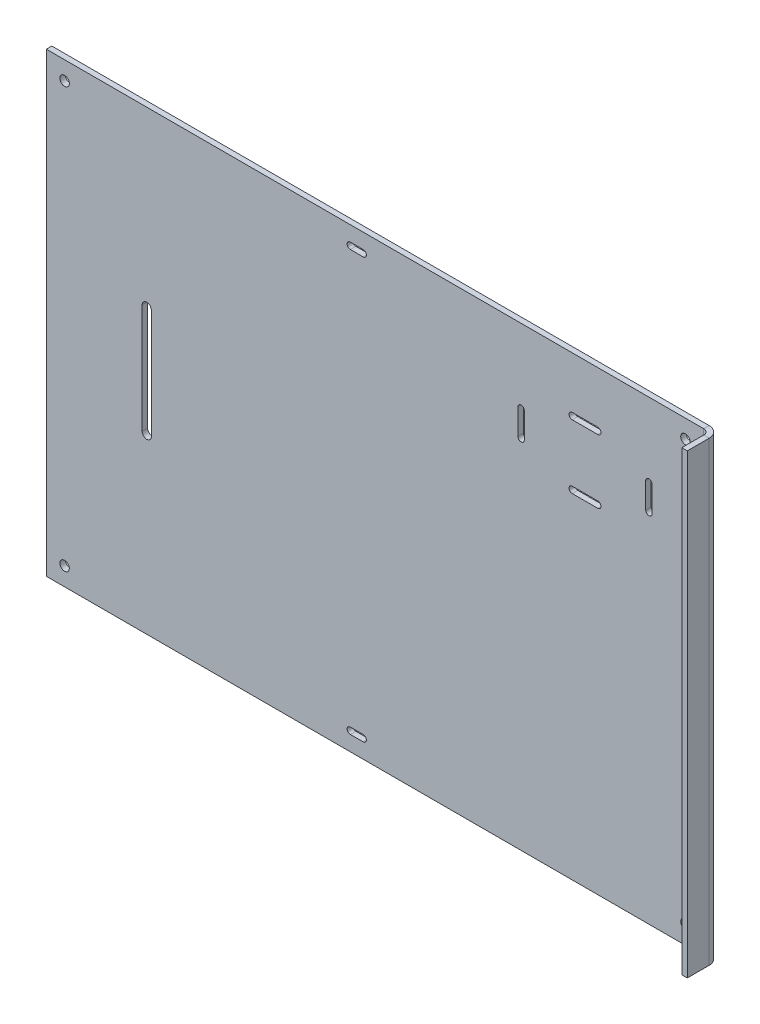
SolidWorks part; units mm, degrees
note: The reader was unsure of these and kept them because the rebuilt part matched: flange length of "Edge-Flange1".
ref_plane "Front Plane" through (0, 0, 0) normal (0, 0, 1) x (1, 0, 0)
ref_plane "Top Plane" through (0, 0, 0) normal (0, 1, 0) x (1, 0, 0)
ref_plane "Right Plane" through (0, 0, 0) normal (1, 0, 0) x (0, 0, -1)
sketch "Sketch1" plane through (0, 0, 0) normal (0, 0, 1) x (1, 0, 0)
  line L0 (180, 125) -> (-180, -125) construction
  line L1 (-180, 125) -> (180, 125)
  line L2 (-180, 125) -> (-180, -125)
  line L3 (-180, -125) -> (180, -125)
  line L4 (180, 125) -> (180, -125)
  point P4 (0, 0)
  dimension "D1" = 360
  dimension "D2" = 250
base flange "Base-Flange1" sketch "Sketch1" thickness 3 reverse thickness direction no parameters "D1"=3
hole_wizard "#6 (0.204) Diameter Slot1" positions "Sketch7" profile "Sketch6" size "#6" standard "ANSI Inch" slot yes end condition through all
sketch "Sketch7" plane through (0, 0, 0) normal (0, 0, 1) x (1, 0, 0)
  line L0 (-180, 125) -> (-180, -125) construction
  line L1 (180, 125) -> (-180, 125) construction
  line L2 (180, -125) -> (180, 125) construction
  line L3 (-180, -125) -> (180, -125) construction
  point P0 (-170, -115)
  point P2 (-170, 115)
  point P4 (170, 115)
  point P6 (170, -115)
  dimension "D1" = 10
  dimension "D2" = 10
  dimension "D3" = 10
  dimension "D4" = 10
  dimension "D5" = 10
  dimension "D6" = 10
  dimension "D7" = 10
  dimension "D8" = 10
sketch "Sketch6" plane through (-170, -115, 0) normal (1, 0, 0) x (0, -1, 0)
  line L0 (0, 0) -> (0, 3)
  line L1 (0, 3) -> (2.5908, 3)
  line L2 (2.5908, 3) -> (2.5908, 0)
  line L5 (2.5908, 0) -> (0, 0)
  line L11 (0, -6.35) -> (0, 107.95) construction
  dimension "Thru Hole Dia." = 5.1816
  dimension "Thru Hole Depth" = 3
sketch "Sketch8" plane through (0, 0, 0) normal (0, 0, 1) x (1, 0, 0)
  line L0 (-13.5, -115) -> (-6.5, -115) construction
  line L1 (-13.5, -113.25) -> (-6.5, -113.25)
  line L2 (-13.5, -116.75) -> (-6.5, -116.75)
  line L3 (-180, -125) -> (180, -125) construction
  line L4 (-180, 125) -> (-180, -125) construction
  arc A0 (-13.5, -113.25) -> (-13.5, -116.75) centre (-13.5, -115) ccw
  arc A1 (-6.5, -116.75) -> (-6.5, -113.25) centre (-6.5, -115) ccw
  point P2 (-10, -115)
  dimension "D1" = 10
  dimension "D2" = 170
extrude "Cut-Extrude1" cut sketch "Sketch8" against normal blind 10
sketch "Sketch9" plane through (0, 0, 0) normal (0, 0, 1) x (1, 0, 0)
  line L0 (-13.5, 115) -> (-6.5, 115) construction
  line L1 (-13.5, 116.75) -> (-6.5, 116.75)
  line L2 (-13.5, 113.25) -> (-6.5, 113.25)
  line L3 (180, 125) -> (-180, 125) construction
  line L4 (-180, 125) -> (-180, -125) construction
  arc A0 (-13.5, 116.75) -> (-13.5, 113.25) centre (-13.5, 115) ccw
  arc A1 (-6.5, 113.25) -> (-6.5, 116.75) centre (-6.5, 115) ccw
  point P2 (-10, 115)
  dimension "D1" = 10
  dimension "D2" = 170
extrude "Cut-Extrude2" cut sketch "Sketch9" against normal blind 10
sketch "Sketch10" plane through (0, 0, 0) normal (0, 0, 1) x (1, 0, 0)
  line L0 (150, 84.5) -> (150, 70.5) construction
  line L1 (151.75, 84.5) -> (151.75, 70.5)
  line L2 (148.25, 84.5) -> (148.25, 70.5)
  line L3 (180, -125) -> (180, 125) construction
  line L4 (180, 125) -> (-180, 125) construction
  arc A0 (151.75, 84.5) -> (148.25, 84.5) centre (150, 84.5) ccw
  arc A1 (148.25, 70.5) -> (151.75, 70.5) centre (150, 70.5) ccw
  point P2 (150, 77.5)
  dimension "D1" = 30
  dimension "D2" = 47.5
extrude "Cut-Extrude4" cut sketch "Sketch10" against normal blind 10
sketch "Sketch11" plane through (0, 0, 0) normal (0, 0, 1) x (1, 0, 0)
  line L0 (108, 95) -> (122, 95) construction
  line L1 (108, 96.75) -> (122, 96.75)
  line L2 (108, 93.25) -> (122, 93.25)
  line L3 (180, 125) -> (-180, 125) construction
  line L4 (180, -125) -> (180, 125) construction
  arc A0 (108, 96.75) -> (108, 93.25) centre (108, 95) ccw
  arc A1 (122, 93.25) -> (122, 96.75) centre (122, 95) ccw
  point P2 (115, 95)
  dimension "D1" = 30
  dimension "D2" = 65
extrude "Cut-Extrude5" cut sketch "Sketch11" against normal blind 10
sketch "Sketch12" plane through (0, 0, 0) normal (0, 0, 1) x (1, 0, 0)
  line L0 (108, 60) -> (122, 60) construction
  line L1 (108, 61.75) -> (122, 61.75)
  line L2 (108, 58.25) -> (122, 58.25)
  line L3 (180, -125) -> (180, 125) construction
  line L4 (180, 125) -> (-180, 125) construction
  arc A0 (108, 61.75) -> (108, 58.25) centre (108, 60) ccw
  arc A1 (122, 58.25) -> (122, 61.75) centre (122, 60) ccw
  point P2 (115, 60)
  dimension "D1" = 65
  dimension "D2" = 65
extrude "Cut-Extrude6" cut sketch "Sketch12" against normal blind 10
sketch "Sketch13" plane through (0, 0, 0) normal (0, 0, 1) x (1, 0, 0)
  line L0 (80, 84.5) -> (80, 70.5) construction
  line L1 (81.75, 84.5) -> (81.75, 70.5)
  line L2 (78.25, 84.5) -> (78.25, 70.5)
  line L3 (180, -125) -> (180, 125) construction
  line L4 (180, 125) -> (-180, 125) construction
  arc A0 (81.75, 84.5) -> (78.25, 84.5) centre (80, 84.5) ccw
  arc A1 (78.25, 70.5) -> (81.75, 70.5) centre (80, 70.5) ccw
  point P2 (80, 77.5)
  dimension "D1" = 100
  dimension "D2" = 47.5
extrude "Cut-Extrude7" cut sketch "Sketch13" against normal blind 10
sketch "Sketch14" plane through (0, 0, 0) normal (0, 0, 1) x (1, 0, 0)
  line L0 (-125, 30) -> (-125, -30) construction
  line L1 (-122.5, 30) -> (-122.5, -30)
  line L2 (-127.5, 30) -> (-127.5, -30)
  line L3 (-180, 125) -> (-180, -125) construction
  line L4 (180, 125) -> (-180, 125) construction
  arc A0 (-122.5, 30) -> (-127.5, 30) centre (-125, 30) ccw
  arc A1 (-127.5, -30) -> (-122.5, -30) centre (-125, -30) ccw
  point P2 (-125, 0)
  dimension "D1" = 55
  dimension "D2" = 125
extrude "Cut-Extrude8" cut sketch "Sketch14" against normal blind 10
edge flange "Edge-Flange1" sketch "Sketch18" flange angle 90 flange length 18 flange position bend outside bend radius 3 thickness 3 parameters "D6"=10
sketch "Sketch18" plane through (180, 0, 0) normal (1, 0, 0) x (0, 1, 0)
  line L2 (-125, 0) -> (-125, 15)
  line L3 (-125, 15) -> (125, 15)
  line L4 (125, 15) -> (125, 0)
  line L11 (-125, 0) -> (125, 0) construction
  line L12 (-125, 0) -> (125, 0)
bend "EdgeBend1" bend radius 3 bend angle 90 parameters "D5"=1
sketch "Bend-Lines1" plane through (0, 0, 0) normal (0, 1, 0) x (1, 0, 0)
sketch "Bounding-Box1" plane through (0, 0, 0) normal (0, 1, 0) x (1, 0, 0)
sheet metal parameters "Sheet-Metal1" thickness 3 parameters "D1"=3
flat pattern "Flat-Pattern1" [suppressed]
sketch "Bend-Lines2" plane through (0, 0, 0) normal (0, 1, 0) x (1, 0, 0)
sketch "Bounding-Box2" [suppressed] plane through (0, 0, 0) normal (0, 1, 0) x (1, 0, 0)
sheet metal parameters "Sheet-Metal2" thickness 3 parameters "D1"=3
flat pattern "Flat-Pattern1"
sketch "Bend-Lines2" plane through (0, 0, 0) normal (0, 1, 0) x (1, 0, 0)
sketch "Bounding-Box2" [suppressed] plane through (0, 0, 0) normal (0, 1, 0) x (1, 0, 0)
sheet metal parameters "Sheet-Metal3" thickness 3 parameters "D1"=3
flat pattern "Flat-Pattern1"
sketch "Bend-Lines2" plane through (0, 0, 0) normal (0, 1, 0) x (1, 0, 0)
sketch "Bounding-Box2" [suppressed] plane through (0, 0, 0) normal (0, 1, 0) x (1, 0, 0)
sheet metal parameters "Sheet-Metal4" thickness 3 parameters "D1"=3
flat pattern "Flat-Pattern1"
sketch "Bend-Lines2" plane through (0, 0, 0) normal (0, 1, 0) x (1, 0, 0)
sketch "Bounding-Box2" [suppressed] plane through (0, 0, 0) normal (0, 1, 0) x (1, 0, 0)
sheet metal parameters "Sheet-Metal6" thickness 3 parameters "D1"=3
flat pattern "Flat-Pattern1"
sketch "Bend-Lines2" plane through (0, 0, 0) normal (0, 1, 0) x (1, 0, 0)
sketch "Bounding-Box2" [suppressed] plane through (0, 0, 0) normal (0, 1, 0) x (1, 0, 0)
sheet metal parameters "Sheet-Metal7" thickness 3 parameters "D1"=3
flat pattern "Flat-Pattern1"
sketch "Bend-Lines2" plane through (0, 0, 0) normal (0, 1, 0) x (1, 0, 0)
sketch "Bounding-Box2" [suppressed] plane through (0, 0, 0) normal (0, 1, 0) x (1, 0, 0)
sheet metal parameters "Sheet-Metal8" thickness 3 parameters "D1"=3
flat pattern "Flat-Pattern1"
sketch "Bend-Lines2" plane through (0, 0, 0) normal (0, 1, 0) x (1, 0, 0)
sketch "Bounding-Box2" [suppressed] plane through (0, 0, 0) normal (0, 1, 0) x (1, 0, 0)
sheet metal parameters "Sheet-Metal9" thickness 3 parameters "D1"=3
flat pattern "Flat-Pattern1"
sketch "Bend-Lines2" plane through (0, 0, 0) normal (0, 1, 0) x (1, 0, 0)
sketch "Bounding-Box2" [suppressed] plane through (0, 0, 0) normal (0, 1, 0) x (1, 0, 0)
sheet metal parameters "Sheet-Metal10" thickness 3 parameters "D1"=3
flat pattern "Flat-Pattern1"
sketch "Bend-Lines2" plane through (0, 0, 0) normal (0, 1, 0) x (1, 0, 0)
sketch "Bounding-Box2" [suppressed] plane through (0, 0, 0) normal (0, 1, 0) x (1, 0, 0)
sheet metal parameters "Sheet-Metal11" thickness 3 parameters "D1"=3
flat pattern "Flat-Pattern1" [suppressed]
sketch "Bend-Lines2" plane through (0, 0, 0) normal (0, 1, 0) x (1, 0, 0)
sketch "Bounding-Box2" [suppressed] plane through (0, 0, 0) normal (0, 1, 0) x (1, 0, 0)
bend of the flat pattern "Flatten-<EdgeBend1>1"
